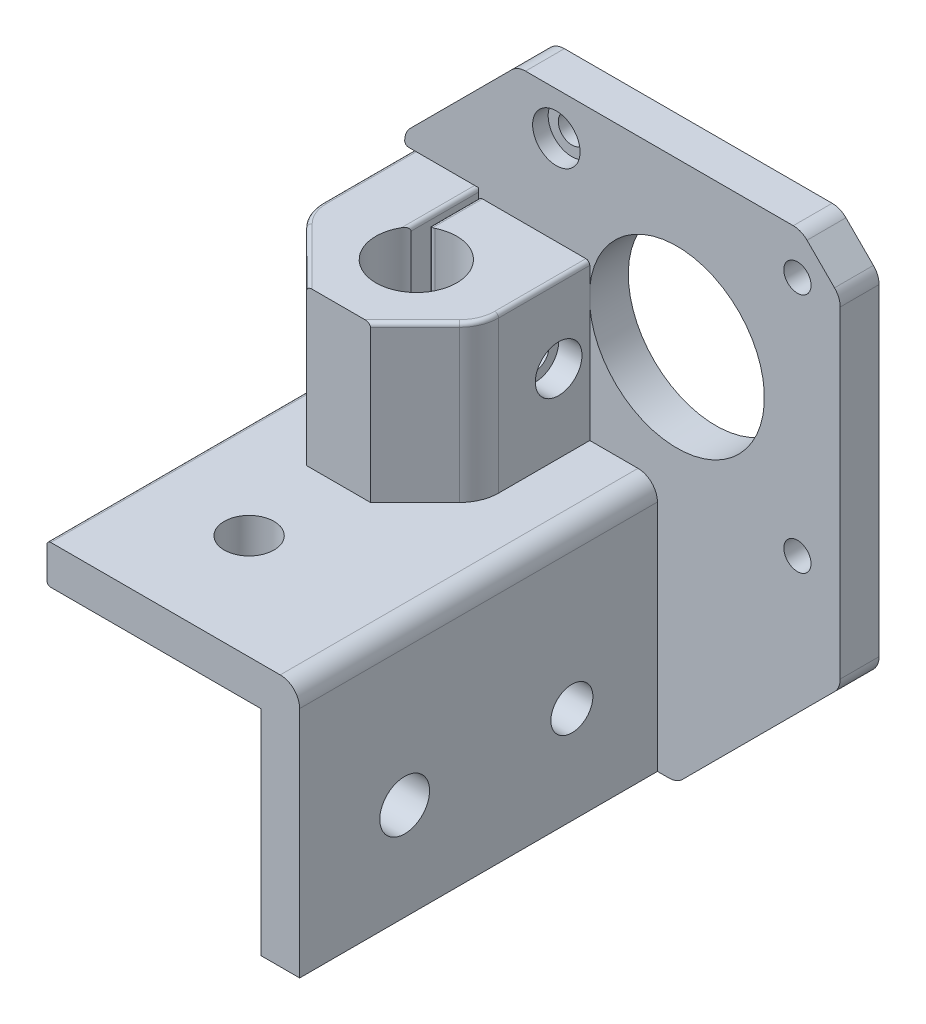
SolidWorks part; units mm, degrees
ref_plane "XY" through (0, 0, 0) normal (0, 0, 1) x (1, 0, 0)
ref_plane "XZ" through (0, 0, 0) normal (0, 1, 0) x (1, 0, 0)
ref_plane "YZ" through (0, 0, 0) normal (1, 0, 0) x (0, 0, -1)
sketch "Sketch1" plane through (0, 0, 0) normal (0, 0, 1) x (1, 0, 0)
  line L0 (-13.5, 34.75) -> (-28, 20.25)
  line L1 (28, 34.75) -> (23, 34.75) construction
  line L2 (28, 34.75) -> (28, 29.75) construction
  line L3 (28, -34.75) -> (7, -34.75) construction
  line L4 (-28, 34.75) -> (-28, 20.25) construction
  line L5 (28, 34.75) -> (-28, -34.75) construction
  line L6 (28, -34.75) -> (-28, 34.75) construction
  line L7 (-0.5, -7.25) -> (-28, -7.25)
  line L8 (-0.5, -7.25) -> (-0.5, -34.75)
  line L9 (-0.5, -34.75) -> (-28, -34.75) construction
  line L10 (-28, -7.25) -> (-28, -34.75) construction
  line L11 (-0.5, -7.25) -> (-28, -34.75) construction
  line L12 (-0.5, -34.75) -> (-28, -7.25) construction
  line L13 (-28, 20.25) -> (-28, -7.25)
  line L14 (-13.5, 34.75) -> (-28, 34.75) construction
  line L15 (23, 34.75) -> (28, 29.75)
  line L16 (23, 34.75) -> (-13.5, 34.75)
  line L17 (28, 29.75) -> (28, -13.75)
  line L18 (28, -13.75) -> (7, -34.75)
  line L19 (7, -34.75) -> (-0.5, -34.75)
  line L20 (28, -13.75) -> (28, -34.75) construction
  line L21 (7, 13.75) -> (7, 41.9826) construction
  line L22 (7, 13.75) -> (59.2876, 13.75) construction
  circle A0 centre (7, 13.75) radius 11.25
  circle A1 centre (-8.5, 29.25) radius 1.75
  circle A2 centre (22.5, 29.25) radius 1.75
  circle A3 centre (22.5, -1.75) radius 1.75
  point P0 (0, 0)
  point P5 (-14.25, -21)
  dimension "D11" = 22.5
  dimension "D14" = 3.5
  dimension "D1" = 69.5
  dimension "D2" = 56
  dimension "D3" = 27.5
  dimension "D4" = 27.5
  dimension "D5" = 14.5
  dimension "D6" = 14.5
  dimension "D7" = 5
  dimension "D8" = 5
  dimension "D9" = 21
  dimension "D10" = 21
  dimension "D12" = 21
  dimension "D13" = 21
  dimension "D15" = 15.5
  dimension "D16" = 15.5
extrude "Boss-Extrude1" add sketch "Sketch1" along normal blind 5
sketch "Sketch2" plane through (0, 0, 5) normal (0, 0, 1) x (1, 0, 0)
  line L0 (-28, -7.25) -> (-0.5, -7.25) construction
  line L1 (-0.5, -7.25) -> (-0.5, -34.75) construction
  line L2 (-28, -7.25) -> (-0.5, -7.25)
  line L3 (-0.5, -7.25) -> (-0.5, -34.75)
  line L4 (-28, -2.25) -> (4.5, -2.25)
  line L5 (4.5, -2.25) -> (4.5, -34.75)
  line L6 (-28, -2.25) -> (-28, -7.25)
  line L7 (-0.5, -34.75) -> (4.5, -34.75)
  dimension "D1" = 5
extrude "Boss-Extrude2" add sketch "Sketch2" along normal blind 46
sketch "Sketch3" plane through (0, -2.25, 0) normal (0, 1, 0) x (1, 0, 0)
  line L0 (-28, -5) -> (-28, -17.6)
  line L1 (4.5, -5) -> (-28, -5) construction
  line L2 (-28, -51) -> (-28, -5) construction
  line L3 (-28, -17.6) -> (-19.6, -26)
  line L4 (-19.6, -26) -> (-11.4, -26)
  line L5 (-11.4, -26) -> (-4.2, -18.8)
  line L7 (-4.2, -18.8) -> (-4.2, -5)
  line L8 (-4.2, -5) -> (-18.5, -5)
  line L9 (-18.5, -5) -> (-18.5, -11.7526)
  line L10 (-28, -5) -> (-19.5, -5)
  line L11 (-19.5, -5) -> (-19.5, -12.6774)
  line L12 (-15.5, -16) -> (-15.5, -32.7142) construction
  arc A0 (-19.5, -12.6774) -> (-18.5, -11.7526) centre (-15.5, -16) ccw
  dimension "D1" = 8.5
  dimension "D5" = 5.2
  dimension "D2" = 14.3
  dimension "D3" = 1
  dimension "D4" = 21
  dimension "D6" = 11
  dimension "D7" = 15.5
  dimension "D8" = 135
  dimension "D9" = 135
  dimension "D10" = 8.2
  dimension "D11" = 4.1
extrude "Boss-Extrude3" add sketch "Sketch3" along normal blind 20
sketch "Sketch4" plane through (0, -2.25, 0) normal (0, 1, 0) x (1, 0, 0)
  line L0 (-28, -51) -> (-28, 0) construction
  line L1 (-28, -17.6) -> (-28, 0)
  line L2 (-28, 0) -> (-0.5, 0) construction
  line L3 (-28, 0) -> (-18.5, 0)
  line L4 (-18.5, -5) -> (-18.5, -11.7526) construction
  line L5 (-18.5, 0) -> (-18.5, -11.7526)
  line L6 (-28, -17.6) -> (-19.6, -26) construction
  line L7 (-28, -17.6) -> (-22.55, -23.05)
  line L8 (-15.5, -16) -> (-30.5819, -31.0819) construction
  line L9 (-15.5, -16) -> (-44.7425, -16) construction
  line L10 (-22.55, -23.05) -> (-19.177, -19.677)
  arc A1 (-18.5, -11.7526) -> (-19.177, -19.677) centre (-15.5, -16) ccw
  dimension "D1" = 45
extrude "Cut-Extrude1" cut sketch "Sketch4" along normal blind 1
sketch "Sketch5" plane through (0, 0, 5) normal (0, 0, 1) x (1, 0, 0)
  line L0 (-19.5, 17.75) -> (-28, 17.75) construction
  line L1 (-19.5, 17.75) -> (-19.5, -1.25) construction
  line L2 (-19.5, 17.75) -> (-28, 17.75)
  line L3 (-19.5, 17.75) -> (-19.5, -1.25)
  line L4 (-18.5, 18.75) -> (-18.5, -1.25)
  line L5 (-18.5, 18.75) -> (-28, 18.75)
  line L6 (-18.5, -1.25) -> (-19.5, -1.25)
  line L7 (-28, 18.75) -> (-28, 17.75)
  dimension "D1" = 1
extrude "Cut-Extrude2" cut sketch "Sketch5" against normal through all
sketch "Sketch6" plane through (4.5, 0, 0) normal (1, 0, 0) x (0, 0, -1)
  circle A0 centre (-16, -22.25) radius 2.7
  circle A1 centre (-37.5, -22.25) radius 3.2
  dimension "D1" = 5.4
  dimension "D2" = 6.4
  dimension "D3" = 21.5
  dimension "D4" = 16
  dimension "D5" = 22.25
extrude "Cut-Extrude3" cut sketch "Sketch6" against normal up to next
sketch "Sketch7" plane through (0, -2.25, 0) normal (0, 1, 0) x (1, 0, 0)
  circle A0 centre (-15.5, -16) radius 5.2
  circle A1 centre (-15.5, -37.5) radius 3.2
  dimension "D1" = 10.4
  dimension "D2" = 6.4
  dimension "D3" = 21.5
extrude "Cut-Extrude4" cut sketch "Sketch7" against normal up to next
sketch "Sketch8" plane through (0, 0, 5) normal (0, 0, 1) x (1, 0, 0)
  circle A0 centre (-8.5, 29.25) radius 3.05
  dimension "D1" = 6.1
extrude "Cut-Extrude5" cut sketch "Sketch8" against normal blind 2
ref_plane "Plane1" through (0, 7.75, 0) normal (0, 1, 0) x (1, 0, 0)
sketch "Sketch9" plane through (0, 7.75, 0) normal (0, 1, 0) x (1, 0, 0)
  line L0 (-38.1403, -9) -> (15.031, -9) construction
  line L1 (23, 0) -> (-13.5, 0) construction
  line L2 (-4.2, -9) -> (-4.2, -6)
  line L3 (-4.2, -18.8) -> (-4.2, -5) construction
  line L4 (-4.2, -18.8) -> (-4.2, -5) construction
  line L5 (-4.2, -6) -> (-7.2, -6)
  line L6 (-7.2, -6) -> (-7.2, -7.25)
  line L7 (-7.2, -7.25) -> (-23, -7.25)
  line L8 (-23, -7.25) -> (-23, -6.65)
  line L9 (-23, -6.65) -> (-27, -6.65)
  line L10 (-27, -6.65) -> (-27, -6.5)
  line L11 (-27, -6.5) -> (-28, -6.5)
  line L12 (-28, 0) -> (-28, -17.6) construction
  line L13 (-28, -6.5) -> (-28, -9)
  line L14 (-28, -9) -> (-4.2, -9)
  dimension "D1" = 9
  dimension "D2" = 3
  dimension "D3" = 1.75
  dimension "D4" = 3
  dimension "D5" = 1
  dimension "D6" = 4
  dimension "D7" = 2.5
  dimension "D8" = 2.35
revolve "Cut-Revolve1" cut sketch "Sketch9" angle 360 about L0
fillet "Fillet1" radius 2.5 7 edges at (4.5, -2.25, 28) (-28, 20.25, 2.5) (7, -34.75, 2.5) (28, -13.75, 2.5) (28, 29.75, 2.5) (23, 34.75, 2.5) (-13.5, 34.75, 2.5)
fillet "Fillet2" radius 5 2 edges at (-28, 8.25, 17.6) (-4.2, 7.75, 18.8)
fillet "Fillet3" radius 0.5 16 edges at (-8.5322, 17.75, 23.1322) (-4.5806, 17.75, 18.6423) (-23.0678, 17.75, 22.5322) (-27.6194, 17.75, 17.4423) (-24.5428, -1.25, 21.0572) (-27.6194, -1.25, 17.4423) (-19.5, -1.25, 6.3387) (-4.2, 17.75, 10.8645) (-18.5, 7.75, 11.7526) (-18.5, 17.75, 8.3763) (-19.5, 17.75, 6.3387) (-28, 17.75, 7.7645) (-28, -1.25, 7.7645) (-28, 18.75, 2.5) (-28, -7.25, 25.5)
